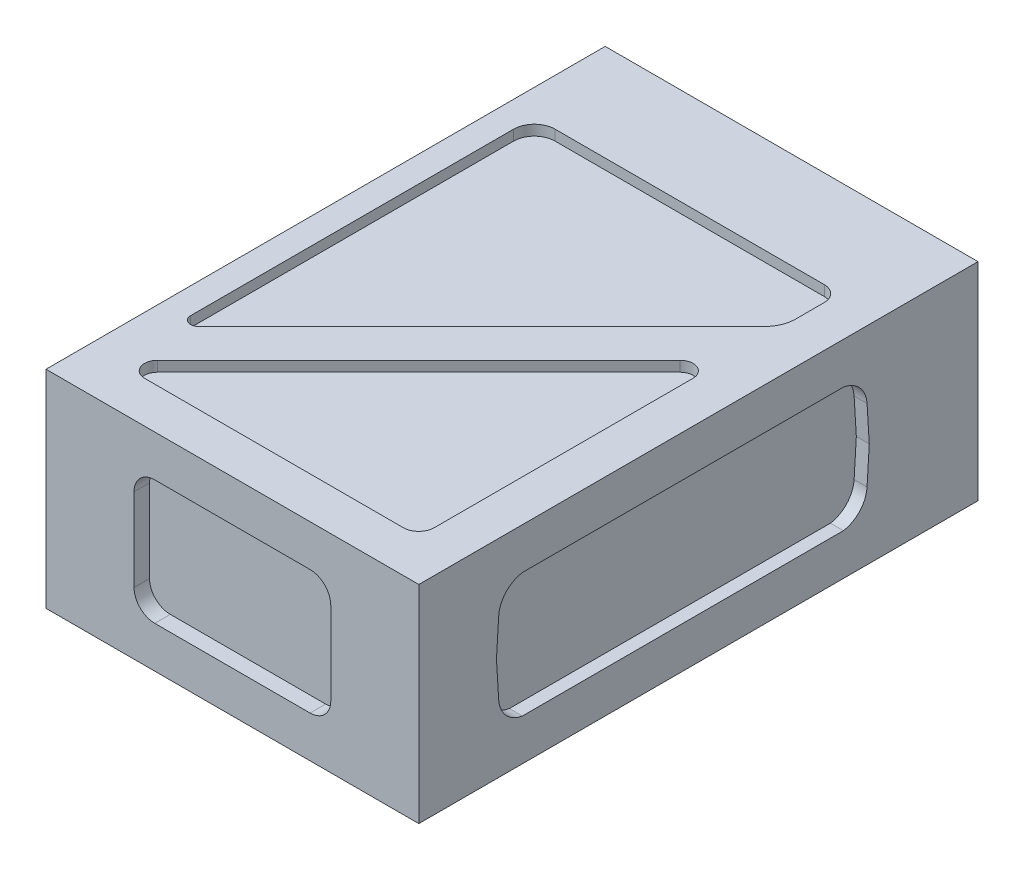
SolidWorks part; units mm, degrees
ref_plane "前视基准面" through (0, 0, 0) normal (0, 0, 1) x (1, 0, 0)
ref_plane "上视基准面" through (0, 0, 0) normal (0, 1, 0) x (1, 0, 0)
ref_plane "右视基准面" through (0, 0, 0) normal (1, 0, 0) x (0, 0, -1)
sketch "草图1" plane through (0, 0, 0) normal (0, 0, 1) x (1, 0, 0)
  line L1 (36, -20) -> (-36, -20)
  line L2 (36, -20) -> (36, 20)
  line L3 (36, 20) -> (-36, 20)
  line L4 (-36, -20) -> (-36, 20)
  line L5 (36, -20) -> (-36, 20) construction
  line L6 (36, 20) -> (-36, -20) construction
  point P0 (0, 0)
  dimension "D1" = 72
  dimension "D2" = 40
extrude "凸台-拉伸1" add sketch "草图1" along normal blind 108
extrude "凸台-拉伸2" add sketch "草图1<2>" along normal blind 105
sketch "草图1<2>" plane through (0, 0, 0) normal (0, 0, 1) x (1, 0, 0) same geometry as "草图1"
sketch "草图2" plane through (-36, 0, 0) normal (-1, 0, 0) x (0, 0, 1)
  line L0 (0, 0) -> (108, 0) construction
  line L1 (108, 20) -> (108, -20) construction
  line L2 (93, 20) -> (93, -20) construction
  line L3 (108, 20) -> (0, 20) construction
  line L4 (108, -20) -> (0, -20) construction
  line L5 (88, 20) -> (88, -16.7281) construction
  line L6 (0, 12) -> (108, 12) construction
  line L7 (0, 20) -> (0, -20) construction
  line L8 (0, -12) -> (108, -12) construction
  line L9 (26, 20) -> (26, -20) construction
  line L10 (26, 12) -> (88, 12)
  line L11 (26, -12) -> (88, -12)
  line L12 (21, 20) -> (21, -20) construction
  line L13 (93, 0) -> (92.5727, 6.9869)
  line L14 (93, 0) -> (92.5727, -6.9869)
  line L15 (57, 12) -> (57, -12) construction
  line L16 (21, 0) -> (21.4273, -6.9869)
  line L17 (21, 0) -> (21.4273, 6.9869)
  arc A0 (92.5727, 6.9869) -> (88, 12) centre (87.1766, 6.6569) ccw
  arc A1 (92.5727, -6.9869) -> (88, -12) centre (87.1766, -6.6569) cw
  arc A2 (21.4273, -6.9869) -> (26, -12) centre (26.8234, -6.6569) ccw
  arc A3 (21.4273, 6.9869) -> (26, 12) centre (26.8234, 6.6569) cw
  dimension "D1" = 15
  dimension "D2" = 5
  dimension "D3" = 12
  dimension "D4" = 82
  dimension "D5" = 5
  dimension "D6" = 7
  dimension "D7" = 3.5
extrude "切除-拉伸1" cut sketch "草图2" against normal blind 2.5
sketch "草图3" plane through (0, 20, 0) normal (0, 1, 0) x (1, 0, 0)
  line L0 (-36, -100) -> (36, -100) construction
  line L1 (-36, -108) -> (-36, 0) construction
  line L2 (36, -108) -> (36, 0) construction
  line L3 (36, -108) -> (-36, -108) construction
  line L4 (-31, 0) -> (-31, -108) construction
  line L5 (36, 0) -> (-36, 0) construction
  line L6 (28, 0) -> (28, -108) construction
  line L7 (25, -100) -> (-24.9645, -100)
  line L8 (-26.7322, -95.7322) -> (23.7322, -45.2678)
  line L9 (28, -29.6863) -> (-31, -88.6863) construction
  line L10 (-36, -18.6863) -> (36, -18.6863) construction
  line L11 (-31, -85.065) -> (-31, -22.6863)
  line L12 (-27, -18.6863) -> (25, -18.6863)
  line L13 (28, -47.0355) -> (28, -97)
  line L14 (28, -21.6863) -> (28, -27.201)
  line L15 (26.2426, -31.4437) -> (-28.4393, -86.1256)
  arc A0 (28, -47.0355) -> (23.7322, -45.2678) centre (25.5, -47.0355) ccw
  arc A1 (-24.9645, -100) -> (-26.7322, -95.7322) centre (-24.9645, -97.5) cw
  arc A2 (25, -100) -> (28, -97) centre (25, -97) ccw
  arc A3 (-31, -22.6863) -> (-27, -18.6863) centre (-27, -22.6863) cw
  arc A4 (-28.4393, -86.1256) -> (-31, -85.065) centre (-29.5, -85.065) cw
  arc A5 (26.2426, -31.4437) -> (28, -27.201) centre (22, -27.201) ccw
  arc A6 (28, -21.6863) -> (25, -18.6863) centre (25, -21.6863) ccw
  point P19 (28, -100)
  point P21 (25.9289, -43)
  point P28 (-26, -94.9289)
  point P31 (-31, -100)
  point P32 (28, -41)
  point P36 (-31, -18.6863)
  point P45 (28, -18.6863)
  dimension "D10" = 2.5
  dimension "D11" = 2.5
  dimension "D6" = 3
  dimension "D9" = 4
  dimension "D12" = 1.5
  dimension "D13" = 6
  dimension "D14" = 3
  dimension "D1" = 8
  dimension "D2" = 5
  dimension "D3" = 8
  dimension "D4" = 59
  dimension "D5" = 45
  dimension "D7" = 8
  dimension "D8" = 70
extrude "切除-拉伸2" cut sketch "草图3" against normal blind 2
ref_plane "基准面1" through (0, 0, 0) normal (0, 1, 0) x (1, 0, 0)
mirror "镜向1" about plane through (0, 0, 0) normal (0, 1, 0) of "切除-拉伸2"
ref_plane "基准面2" through (0, 0, 0) normal (-1, 0, 0) x (0, 0, 1)
mirror "镜向2" about plane through (0, 0, 0) normal (-1, 0, 0) of "切除-拉伸1"
sketch "草图5" plane through (0, 0, 108) normal (0, 0, 1) x (1, 0, 0)
  line L1 (15, -12) -> (-15, -12)
  line L2 (19, -8) -> (19, 8)
  line L3 (15, 12) -> (-15, 12)
  line L4 (-19, -8) -> (-19, 8)
  line L5 (19, -12) -> (-19, 12) construction
  line L6 (19, 12) -> (-19, -12) construction
  arc A0 (-19, 8) -> (-15, 12) centre (-15, 8) cw
  arc A1 (-15, -12) -> (-19, -8) centre (-15, -8) cw
  arc A2 (19, 8) -> (15, 12) centre (15, 8) ccw
  arc A3 (15, -12) -> (19, -8) centre (15, -8) ccw
  point P0 (0, 0)
  point P1 (0, 0)
  dimension "D3" = 4
  dimension "D4" = 4
  dimension "D5" = 4
  dimension "D6" = 4
  dimension "D1" = 38
  dimension "D2" = 24
extrude "切除-拉伸3" cut sketch "草图5" against normal blind 3
